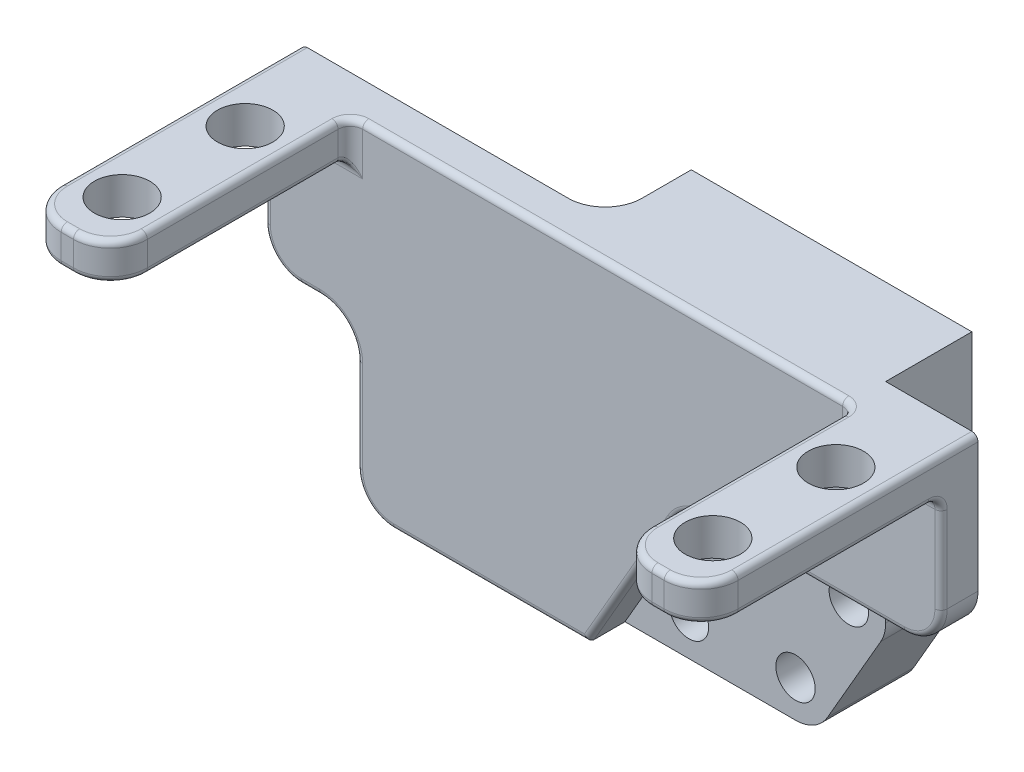
SolidWorks part; units mm, degrees
note: The reader was unsure of these and kept them because the rebuilt part matched: shared geometry of "Sketch1<5>", "Sketch1<6>".
ref_plane "Front Plane" through (0, 0, 0) normal (0, 0, 1) x (1, 0, 0)
ref_plane "Top Plane" through (0, 0, 0) normal (0, 1, 0) x (1, 0, 0)
ref_plane "Right Plane" through (0, 0, 0) normal (1, 0, 0) x (0, 0, -1)
sketch "Sketch1" plane through (0, 0, 0) normal (0, 0, 1) x (1, 0, 0)
  line L0 (18.1959, -5.9286) -> (18.1959, -19.9286)
  line L1 (12.5979, -33.4286) -> (-21.8041, -33.4286)
  line L2 (-4.6031, -5.9286) -> (-4.6031, -33.4286)
  line L3 (-21.8041, -5.9286) -> (-21.8041, -25.9286) construction
  line L4 (-22.3041, -5.9286) -> (-22.3041, -8.9286)
  line L5 (18.1959, -23.7324) -> (18.1959, -5.9286)
  line L7 (-26.3041, -5.9286) -> (-21.7206, -5.9286) construction
  line L9 (-29.3041, -5.9286) -> (-29.3041, -2.9286) construction
  line L11 (25.6959, -5.9286) -> (25.6959, -2.9286) construction
  line L12 (-29.3041, -5.9286) -> (25.6959, -5.9286)
  line L13 (-21.8041, -5.9286) -> (-21.8041, -33.4286)
  line L14 (-2.9906, -33.4286) -> (4.8036, -19.9286)
  line L15 (4.8036, -19.9286) -> (18.1959, -19.9286)
  line L16 (12.5979, -33.4286) -> (18.1959, -23.7324)
  line L17 (6.5357, -22.9286) -> (2.2056, -30.4286) construction
  line L18 (15.1959, -22.9286) -> (10.8658, -30.4286) construction
  line L19 (-29.3041, -5.9286) -> (-29.3041, -19.9286)
  line L20 (-29.3041, -19.9286) -> (25.6959, -19.9286) construction
  line L21 (25.6959, -19.9286) -> (25.6959, -5.9286)
  line L22 (-29.3041, -8.9286) -> (-21.8041, -8.9286)
  line L23 (18.1959, -8.9286) -> (25.6959, -8.9286)
  line L24 (-29.3041, -19.9286) -> (-21.8041, -19.9286)
  line L25 (25.6959, -19.9286) -> (18.1959, -19.9286)
  line L26 (18.6959, -5.9286) -> (18.6959, -8.9286)
  circle A4 centre (2.2056, -30.4286) radius 1.6
  circle A5 centre (6.5357, -22.9286) radius 1.6
  circle A6 centre (15.1959, -22.9286) radius 1.6
  circle A7 centre (10.8658, -30.4286) radius 1.6
  dimension "D2" = 3
  dimension "D3" = 3
  dimension "D4" = 3
  dimension "D5" = 3
  dimension "D6" = 3
  dimension "D7" = 3
  dimension "D1" = 7
  dimension "D8" = 7
  dimension "D9" = 7.5
extrude "Boss-Extrude1" add sketch "Sketch1" along normal blind 7
extrude "Boss-Extrude3" add sketch "Sketch1<5>" along normal blind 3 from surface at 7 starting at face at (7.9567, -20.4894, 7)
sketch "Sketch1<5>" plane through (0, 0, 0) normal (0, 0, 1) x (1, 0, 0) same geometry as "Sketch1"
extrude "Boss-Extrude4" add sketch "Sketch1<6>" along normal blind 19.5 from surface at 10 contours L19 L22 L13 L12 | L0 L23 L21 L12
sketch "Sketch1<6>" plane through (0, 0, 0) normal (0, 0, 1) x (1, 0, 0) same geometry as "Sketch1"
sketch "Sketch2" plane through (0, -5.9286, 0) normal (0, 1, 0) x (1, 0, 0)
  line L0 (-25.8041, -29.5) -> (-25.8041, -6) construction
  line L1 (-29.3041, -29.5) -> (-22.3041, -29.5) construction
  line L2 (-1.8041, -20.05) -> (-29.3041, -20.05) construction
  line L3 (-1.8041, -10) -> (-1.8041, -30.1) construction
  line L4 (-30.6827, -30.1) -> (28.3279, -30.1) construction
  line L8 (-4.6031, -7) -> (-29.3041, -7)
  line L9 (-4.6031, -7) -> (-29.3041, -7)
  line L12 (18.1959, 0) -> (-4.6031, 0)
  line L13 (-4.6031, 0) -> (-4.6031, -7)
  line L14 (-29.3041, -7) -> (-29.3041, -29.5)
  line L15 (-29.3041, -7) -> (-29.3041, -29.5)
  line L18 (-22.3041, -10) -> (18.6959, -10)
  line L19 (-22.3041, -10) -> (18.6959, -10)
  line L23 (18.1959, -7) -> (18.1959, 0)
  line L24 (18.1959, 0) -> (-4.6031, 0) construction
  line L35 (18.1959, -7) -> (18.1959, 0) construction
  line L37 (-29.3041, -29.5) -> (-22.3041, -29.5)
  line L38 (-29.3041, -29.5) -> (-22.3041, -29.5)
  line L39 (18.6959, -29.5) -> (25.6959, -29.5)
  line L40 (18.6959, -29.5) -> (25.6959, -29.5)
  line L41 (25.6959, -29.5) -> (25.6959, -7)
  line L42 (25.6959, -29.5) -> (25.6959, -7)
  line L43 (25.6959, -7) -> (18.1959, -7)
  line L44 (25.6959, -7) -> (18.1959, -7)
  line L45 (-22.3041, -29.5) -> (-22.3041, -10)
  line L46 (-22.3041, -29.5) -> (-22.3041, -10)
  line L47 (18.6959, -10) -> (18.6959, -29.5)
  line L48 (18.6959, -10) -> (18.6959, -29.5)
  line L50 (-4.6031, 0) -> (-4.6031, -7)
  circle A0 centre (-25.8041, -15.05) radius 2.25
  circle A1 centre (-25.8041, -25.05) radius 2.25
  circle A2 centre (22.1959, -15.05) radius 2.25
  circle A3 centre (22.1959, -25.05) radius 2.25
  dimension "D4" = 4.5
  dimension "D5" = 4.5
  dimension "D2" = 5
  dimension "D3" = 5
  dimension "D6" = 0.6
  dimension "D1" = 0
extrude "Cut-Extrude1" cut sketch "Sketch2" against normal up to next contours A2 | A0 | A1 | A3
fillet "Fillet1" radius 3 11 edges at (-22.3041, -7.4286, 29.5) (18.6959, -7.4286, 29.5) (-29.3041, -7.4286, 29.5) (25.6959, -7.4286, 29.5) (4.8036, -19.9286, 8.5) (18.1959, -23.7324, 3.5) (12.5979, -33.4286, 3.5) (25.6959, -19.9286, 8.5) (-21.8041, -19.9286, 8.5) (-29.3041, -19.9286, 8.5) (-21.8041, -33.4286, 8.5)
fillet "Fillet2" radius 1 4 edges at (18.6959, -7.4286, 10) (22.1959, -8.9286, 10) (-22.3041, -7.4286, 10) (-25.8041, -8.9286, 10)
fillet "Fillet3" radius 0.5 39 edges at (-29.3041, -5.9286, 16.75) (-28.4254, -5.9286, 28.6213) (-25.8041, -5.9286, 29.5) (-23.1827, -5.9286, 28.6213) (-22.3041, -5.9286, 18.75) (-22.0112, -5.9286, 10.2929) (-1.8041, -5.9286, 10) (18.403, -5.9286, 10.2929) (18.6959, -5.9286, 18.75) (19.5746, -5.9286, 28.6213) (22.1959, -5.9286, 29.5) (24.8173, -5.9286, 28.6213) (25.6959, -5.9286, 16.75) (18.403, -9.2215, 10.2929) (18.6959, -8.9286, 18.75) (19.5746, -8.9286, 28.6213) (22.1959, -8.9286, 29.5) (24.8173, -8.9286, 28.6213) (-22.0112, -9.2215, 10.2929) (-22.3041, -8.9286, 18.75) (-23.1827, -8.9286, 28.6213) (-25.8041, -8.9286, 29.5) (-28.4254, -8.9286, 28.6213) (-29.3041, -8.9286, 18.75) (-29.3041, -9.2215, 10.2929) (-29.3041, -13.4286, 10) (-28.4254, -19.0499, 10) (-25.5541, -19.9286, 10) (-22.6827, -20.8073, 10) (-21.8041, -26.6786, 10) (-10.8973, -33.4286, 10) (0.4735, -27.4286, 10) (5.0357, -20.3305, 10) (14.6158, -19.9286, 10) (24.8173, -19.0499, 10) (25.6959, -13.4286, 10) (25.6959, -9.2215, 10.2929) (25.6959, -8.9286, 18.75) (-20.9254, -32.5499, 10)
fillet "Fillet4" radius 3 1 edges at (-4.6031, -19.6786, 7)
